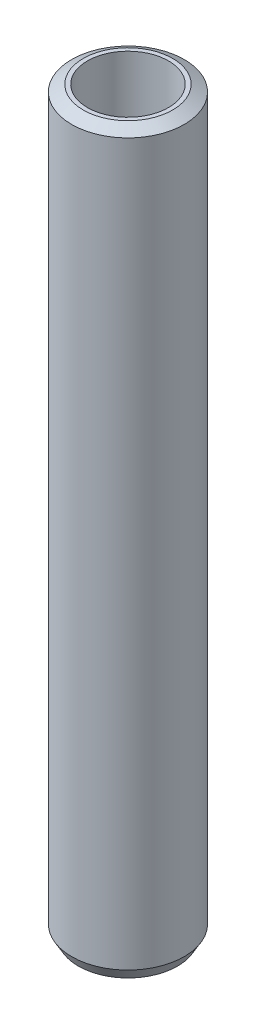
SolidWorks part; units mm, degrees
ref_plane "Front Plane" through (0, 0, 0) normal (0, 0, 1) x (1, 0, 0)
ref_plane "Top Plane" through (0, 0, 0) normal (0, 1, 0) x (1, 0, 0)
ref_plane "Right Plane" through (0, 0, 0) normal (1, 0, 0) x (0, 0, -1)
sketch "Sketch1" plane through (0, 0, 0) normal (0, 1, 0) x (1, 0, 0)
  circle A0 centre (0, 0) radius 20
  dimension "SHAFT_OD" = 40
extrude "Boss-Extrude1" add sketch "Sketch1" along normal blind 262.5184
sketch "Sketch2" plane through (0, 0, 0) normal (0, 1, 0) x (1, 0, 0)
  circle A0 centre (0, 0) radius 14.39
  dimension "BORE_D" = 28.7799
extrude "Cut-Extrude1" cut sketch "Sketch2" along normal through all
chamfer "Chamfer1" distance 2.3792 angle 60 2 edges at (0, 262.5184, 20) (0, 0, 20) first distance on face at (0, 262.5184, 20) first distance on face at (0, 0, 14.39)
